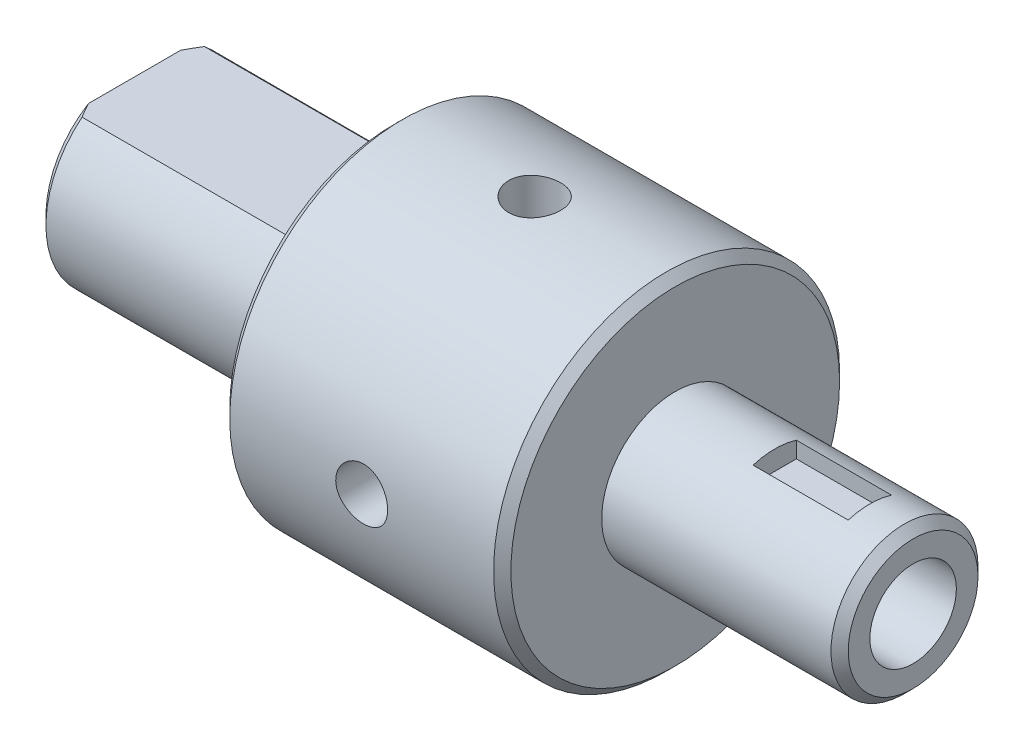
SolidWorks part; units mm, degrees
ref_plane "Спереди" through (0, 0, 0) normal (0, 0, 1) x (1, 0, 0)
ref_plane "Сверху" through (0, 0, 0) normal (0, 1, 0) x (1, 0, 0)
ref_plane "Справа" through (0, 0, 0) normal (1, 0, 0) x (0, 0, -1)
sketch "Эскиз1" plane through (0, 0, 0) normal (0, 0, 1) x (1, 0, 0)
  line L1 (0, 10) -> (0, 22.5)
  line L2 (0, 22.5) -> (60, 22.5)
  line L3 (60, 22.5) -> (60, 40)
  line L4 (60, 40) -> (125, 40)
  line L5 (125, 40) -> (125, 17)
  line L6 (125, 17) -> (180, 17)
  line L7 (180, 17) -> (180, 10)
  line L9 (0, 0) -> (-45.0163, 0) construction
  line L10 (0, 10) -> (180, 10)
  dimension "D1" = 80
  dimension "D2" = 45
  dimension "D3" = 34
  dimension "D4" = 180
  dimension "D5" = 60
  dimension "D6" = 65
  dimension "D7" = 20
revolve "Повернуть1" add sketch "Эскиз1" angle 360 about L9
sketch "Эскиз6" plane through (0, 0, 0) normal (0, 0, 1) x (1, 0, 0)
  line L0 (60, 22.5) -> (0, 22.5) construction
  line L1 (148, 17) -> (170, 17)
  line L2 (148, 17) -> (148, 12.5)
  line L3 (148, 12.5) -> (170, 12.5)
  line L4 (170, 17) -> (170, 12.5)
  line L8 (180, 17) -> (125, 17) construction
  line L9 (180, -17) -> (180, 17) construction
  line L10 (0, 17.5) -> (50, 17.5)
  line L11 (0, 22.5) -> (0, -22.5) construction
  line L12 (50, 17.5) -> (50, 22.5)
  line L13 (50, 22.5) -> (0, 22.5)
  line L14 (0, 22.5) -> (0, 17.5)
  line L15 (0, -22.5) -> (60, -22.5) construction
  dimension "D1" = 22
  dimension "D2" = 10
  dimension "D3" = 4.5
  dimension "D4" = 50
  dimension "D5" = 40
extrude "Вырез-Вытянуть4" cut sketch "Эскиз6" against normal mid plane 10 contours L4 L1 L2 L3 region at (159, 14.75, 0)
extrude "Вырез-Вытянуть11" cut sketch "Эскиз6<3>" against normal through all both and the other way through all contours L13 L14 L10 L12 region at (25, 20, 0)
sketch "Эскиз6<3>" plane through (0, 0, 0) normal (0, 0, 1) x (1, 0, 0) same geometry as "Эскиз6"
sketch "Эскиз16" plane through (0, 0, 0) normal (0, 1, 0) x (1, 0, 0)
  line L0 (60, 0) -> (125, 0) construction
  line L2 (125, -17) -> (125, 17) construction
  line L3 (60, 22.5) -> (60, -22.5) construction
  circle A0 centre (92.5, 0) radius 6
  dimension "D1" = 12
  dimension "D2" = 32.5
extrude "Вырез-Вытянуть10" cut sketch "Эскиз16" against normal through all both and the other way through all
pattern_circular "Круговой массив1" count 4 over 360 about axis through (0, 0, 0) along (1, 0, 0) of "Вырез-Вытянуть10"
chamfer "Фаска3" distance 2 angle 45 4 edges at (180, 0, -17) (0, -22.5, 0) (125, 0, -40) (60, 0, -40)
